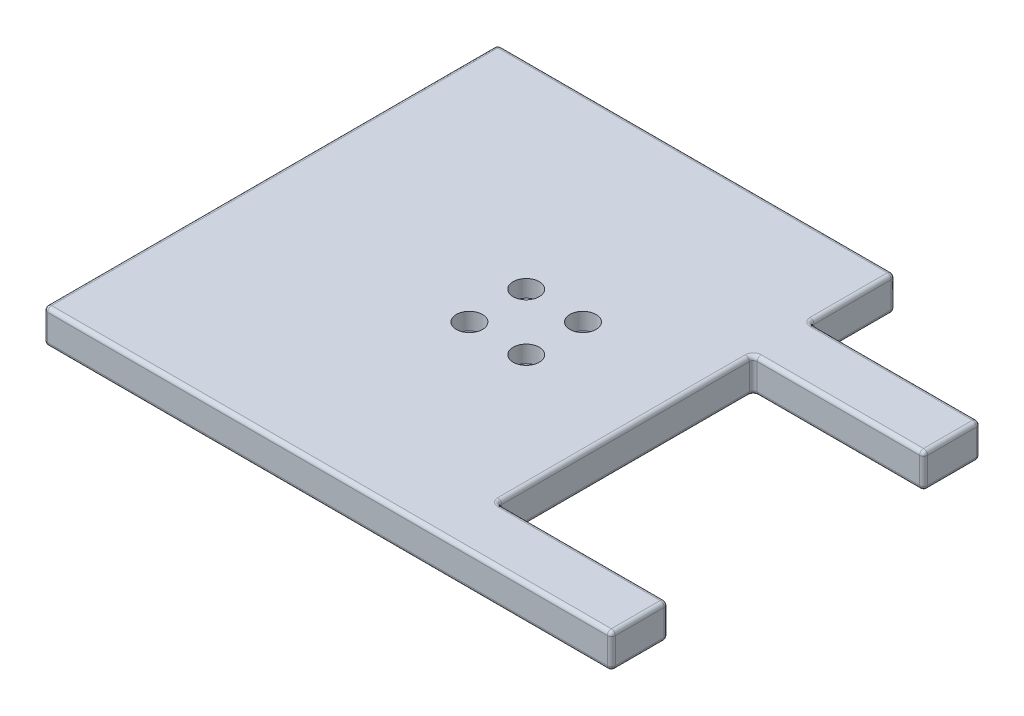
SolidWorks part; units mm, degrees
ref_plane "前视基准面" through (0, 0, 0) normal (0, 0, 1) x (1, 0, 0)
ref_plane "上视基准面" through (0, 0, 0) normal (0, 1, 0) x (1, 0, 0)
ref_plane "右视基准面" through (0, 0, 0) normal (1, 0, 0) x (0, 0, -1)
other "Configuration Table"
sketch "草图1" plane through (0, 0, 0) normal (0, 1, 0) x (1, 0, 0)
  line L1 (-60, 40) -> (10, 40)
  line L2 (-60, 40) -> (-60, -40)
  line L3 (-60, -40) -> (40, -40)
  line L4 (40, 25) -> (40, 15)
  line L5 (-55, 0) -> (55, 0) construction
  line L7 (10, 40) -> (10, 25)
  line L8 (10, 25) -> (40, 25)
  line L9 (0, -55) -> (0, 55) construction
  line L10 (40, 15) -> (10, 15)
  line L11 (10, 15) -> (10, -30)
  line L12 (10, -30) -> (40, -30)
  line L13 (40, -30) -> (40, -40)
  dimension "D1" = 10
  dimension "D2" = 40
  dimension "D3" = 40
  dimension "D4" = 80
  dimension "D5" = 10
  dimension "D6" = 15
  dimension "D7" = 10
  dimension "D8" = 60
  dimension "D9" = 10
extrude "凸台-拉伸1" add sketch "草图1" along normal blind 6
sketch "草图6" plane through (0, 0, 0) normal (0, -1, 0) x (-1, 0, 0)
  line L0 (-3.3, 0) -> (3.3, 0) construction
  line L1 (60, 40) -> (60, -40) construction
  point P0 (15, 0)
  dimension "D1" = 45
ref_axis "基准轴1" through (-15, 0, 0) along (0, -1, 0)
fillet "圆角2" radius 0.7 30 edges at (-25, 6, -40) (25, 6, -25) (40, 6, -20) (40, 3, -25) (10, 3, -25) (10, 3, 30) (25, 6, 30) (40, 6, 35) (40, 3, 30) (10, 3, -40) (10, 6, -32.5) (10, 6, 7.5) (10, 3, -15) (40, 0, 35) (40, 3, 40) (-10, 6, 40) (-60, 3, 40) (-60, 6, 0) (-60, 3, -40) (-60, 0, 0) (-25, 0, -40) (10, 0, -32.5) (25, 0, -25) (40, 0, -20) (40, 3, -15) (25, 6, -15) (25, 0, -15) (10, 0, 7.5) (25, 0, 30) (-10, 0, 40)
sketch "草图7" plane through (0, 0, 0) normal (0, -1, 0) x (1, 0, 0)
  point P0 (-20, 5)
  point P1 (-20, -5)
  point P3 (-10, 5)
  point P4 (-10, -5)
  dimension "D1" = 5
  dimension "D2" = 5
  dimension "D3" = 10
  dimension "D4" = 5
  dimension "D5" = 5
  dimension "D6" = 5
  dimension "D7" = 5
  dimension "D8" = 5
hole_wizard "M2 六角头机械螺钉的柱形沉头孔1" positions "草图8" profile "草图9" counterbore size "M2" standard "ANSI Metric" end condition up to next
sketch "草图8" plane through (0, 6, 0) normal (0, 1, 0) x (1, 0, 0)
  point P0 (-20, 5)
  point P3 (-10, 5)
  point P6 (-10, -5)
  point P9 (-20, -5)
sketch "草图9" plane through (-20, 6, -5) normal (1, 0, 0) x (0, 0, 1)
  line L0 (0, 0) -> (0, 6)
  line L1 (0, 6) -> (1.1, 6)
  line L3 (1.1, 6) -> (1.1, 3)
  line L4 (1.1, 3) -> (2.3, 3)
  line L5 (2.3, 3) -> (2.3, 0)
  line L7 (2.3, 0) -> (0, 0)
  line L11 (0, -6.35) -> (0, 107.95) construction
  dimension "通孔孔直径" = 2.2
  dimension "通孔孔深度" = 6
  dimension "柱形沉头孔直径" = 4.6
  dimension "柱形沉头孔深度" = 3
